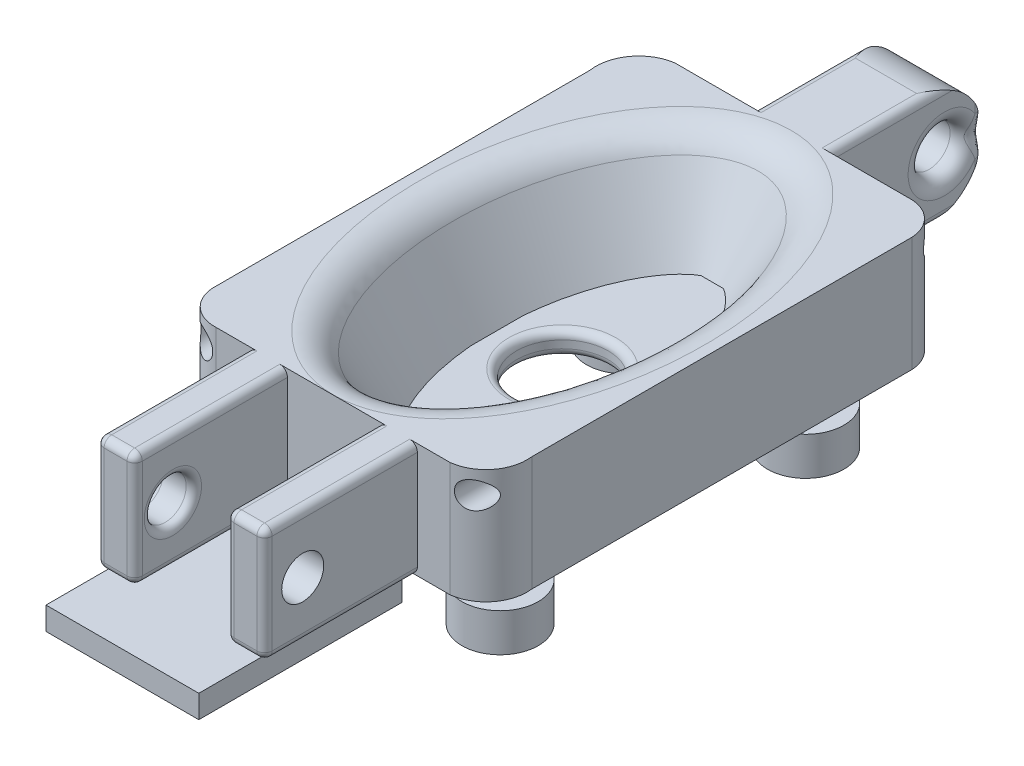
SolidWorks part; units mm, degrees
ref_plane "Front Plane" through (0, 0, 0) normal (0, 0, 1) x (1, 0, 0)
ref_plane "Top Plane" through (0, 0, 0) normal (0, 1, 0) x (1, 0, 0)
ref_plane "Right Plane" through (0, 0, 0) normal (1, 0, 0) x (0, 0, -1)
sketch "Sketch1" plane through (0, 0, 0) normal (0, 1, 0) x (1, 0, 0)
  line L1 (-15.3125, -30) -> (15.3125, -30)
  line L2 (-20, -25.7813) -> (-20, 23.5937)
  line L3 (-15.3125, 30) -> (15.3125, 30)
  line L4 (20, -24.0015) -> (20, 25.7812)
  line L5 (-20, -30) -> (20, 30) construction
  line L6 (-20, 30) -> (20, -30) construction
  arc A0 (-15.3125, 30) -> (-20, 23.5937) centre (-14.4531, 24.4531) ccw
  arc A1 (15.3125, 30) -> (20, 25.7812) centre (15.5469, 25.5469) cw
  arc A2 (15.3125, -30) -> (20, -24.0015) centre (14.657, -24.657) ccw
  arc A3 (-15.3125, -30) -> (-20, -25.7813) centre (-15.5469, -25.5469) cw
  point P0 (0, 0)
  dimension "D1" = 40
  dimension "D2" = 60
extrude "Boss-Extrude1" add sketch "Sketch1" along normal blind 15
sketch "Sketch2" plane through (0, 0, 30) normal (0, 0, 1) x (1, 0, 0)
  line L0 (-20, 15) -> (-20, 0) construction
  line L1 (20.0401, 0) -> (20.0401, 15) construction
  line L2 (15.3125, 0) -> (20.0401, 0) construction
  line L3 (-20, 0) -> (-15.3125, 0) construction
  circle A0 centre (-17.5, 12) radius 1.75
  circle A1 centre (17.5401, 12) radius 1.75
  dimension "D1" = 2.5
  dimension "D5" = 3.5
  dimension "D6" = 3.5
  dimension "D2" = 2.5
  dimension "D3" = 12
  dimension "D4" = 12
sketch "Sketch4" plane through (0, 15, 0) normal (0, 1, 0) x (1, 0, 0)
  ellipse E0 centre (0, 0) end of major axis (0, 27.1105) minor radius 15.7856
extrude "Cut-Extrude6" cut sketch "Sketch4" against normal blind 15 draft 30.5
fillet "Fillet4" radius 5 1 edges at (-2.7969, 15, -26.6816)
extrude "Cut-Extrude7" cut sketch "Sketch2" against normal blind 150
sketch "Sketch5" plane through (0, 0, 0) normal (0, -1, 0) x (1, 0, 0)
  line L1 (7.7139, -19.6019) -> (-8.5645, -19.6019)
  line L2 (7.7139, -19.6019) -> (7.7139, 20.1727)
  line L3 (7.7139, 20.1727) -> (-8.5645, 20.1727)
  line L4 (-8.5645, -19.6019) -> (-8.5645, 20.1727)
extrude "Boss-Extrude2" add sketch "Sketch5" against normal blind 3
sketch "Sketch6" plane through (0, 3, 0) normal (0, 1, 0) x (1, 0, 0)
  circle A0 centre (0, 0) radius 6
extrude "Cut-Extrude8" cut sketch "Sketch6" against normal blind 3
sketch "Sketch8" plane through (0, 0, -30) normal (0, 0, -1) x (-1, 0, 0)
  line L7 (-5, 15) -> (5, 15)
  line L8 (-5, 15) -> (-5, 0)
  line L9 (-5, 0) -> (5, 0)
  line L10 (5, 15) -> (5, 0)
  point P9 (0, 7.5)
extrude "Boss-Extrude3" add sketch "Sketch8" along normal blind 20
sketch "Sketch10" plane through (-5, 0, 0) normal (-1, 0, 0) x (0, 0, 1)
  line L0 (-50, 0) -> (-50, 15) construction
  line L1 (-50, 15) -> (-30, 15) construction
  circle A0 centre (-45, 7.32) radius 2.75
  dimension "D1" = 5
  dimension "D3" = 5.5
  dimension "D2" = 7.68
extrude "Cut-Extrude9" cut sketch "Sketch10" against normal blind 20
fillet "Fillet8" radius 2 1 edges at (5, 4.57, -45)
fillet "Fillet9" radius 1 1 edges at (-5, 4.57, -45)
fillet "Fillet11" radius 1 1 edges at (0, 15, -50)
fillet "Fillet12" radius 1 3 edges at (-5, 15, -39.5) (-5, 14.7071, -49.7071) (-5, 7, -50)
fillet "Fillet13" radius 1 3 edges at (5, 7, -50) (5, 15, -39.5) (5, 14.7071, -49.7071)
fillet "Fillet14" radius 1 5 edges at (-5, 0, -39.5) (-4.7071, 0, -49.7071) (5, 0, -39.5) (0, 0, -50) (4.7071, 0, -49.7071)
sketch "Sketch11" plane through (0, 0, 30) normal (0, 0, 1) x (1, 0, 0)
  line L3 (-10.98, 0) -> (-5.98, 0)
  line L10 (6.02, 0) -> (11.02, 0)
  line L15 (-5.98, 15) -> (-5.98, 0)
  line L20 (6.02, 15) -> (6.02, 0)
  line L25 (6.02, 0) -> (11.02, 0)
  line L26 (6.02, 0) -> (6.02, 15)
  line L27 (6.02, 15) -> (11.02, 15)
  line L28 (11.02, 0) -> (11.02, 15)
  line L30 (-5.98, 15) -> (-10.98, 15)
  line L31 (-5.98, 15) -> (-5.98, 0)
  line L32 (-5.98, 0) -> (-10.98, 0)
  line L33 (-10.98, 15) -> (-10.98, 0)
  point P7 (0.02, 7.5)
  line M22 (-15.3125, 0) -> (15.3125, 0)
  line M24 (15.3125, 15) -> (-15.3125, 15)
  dimension "D7" = 5
extrude "Boss-Extrude4" add sketch "Sketch11" along normal blind 20 contours L33 L15 M24 M22 | L28 L20 M22 M24
sketch "Sketch12" plane through (-10.98, 0, 0) normal (-1, 0, 0) x (0, 0, 1)
  line L0 (50, 0) -> (50, 15) construction
  line L1 (50, 15) -> (30, 15) construction
  circle A0 centre (45, 7.32) radius 2.75
  dimension "D1" = 5
  dimension "D3" = 5.5
  dimension "D2" = 7.68
extrude "Cut-Extrude10" cut sketch "Sketch12" against normal blind 250
fillet "Fillet17" radius 1 1 edges at (-10.98, 4.57, 45)
fillet "Fillet18" radius 1 1 edges at (-5.98, 7.32, 42.25)
fillet "Fillet19" radius 1 1 edges at (-5.98, 0, 40)
fillet "Fillet20" radius 1 3 edges at (-5.98, 8, 50) (-8.98, 0, 50) (-6.2729, 0.2929, 50)
fillet "Fillet21" radius 1 3 edges at (-10.98, 8, 50) (-10.98, 0, 39.5) (-10.98, 0.2929, 49.7071)
fillet "Fillet22" radius 1 5 edges at (-5.98, 15, 39.5) (-8.48, 15, 50) (-6.2729, 15, 49.7071) (-10.98, 15, 39.5) (-10.6871, 15, 49.7071)
fillet "Fillet23" radius 1 1 edges at (6.02, 0, 40)
fillet "Fillet25" radius 1 3 edges at (6.02, 8, 50) (9.02, 0, 50) (6.3129, 0.2929, 50)
fillet "Fillet26" radius 1 3 edges at (11.02, 0, 39.5) (11.02, 8, 50) (11.02, 0.2929, 49.7071)
fillet "Fillet27" radius 1 5 edges at (6.02, 15, 39.5) (6.3129, 15, 49.7071) (11.02, 15, 39.5) (8.52, 15, 50) (10.7271, 15, 49.7071)
fillet "Fillet28" radius 1 1 edges at (6.02, 7.32, 42.25)
fillet "Fillet29" radius 1 1 edges at (0, 0, 6)
fillet "Fillet30" radius 1 1 edges at (0, 3, 6)
sketch "Sketch13" plane through (0, 0, 0) normal (0, -1, 0) x (1, 0, 0)
  line L0 (-20, -23.5937) -> (-20, 25.7813) construction
  line L1 (20, 24.0015) -> (20, -25.7812) construction
  circle A0 centre (-11.8492, 20) radius 2.5
  circle A1 centre (11.85, 20) radius 2.5
  circle A2 centre (-11.8492, -20) radius 2.5
  circle A3 centre (11.85, -20) radius 2.5
  dimension "D1" = 5
  dimension "D4" = 5
  dimension "D7" = 5
  dimension "D8" = 5
  dimension "D2" = 8.1508
  dimension "D3" = 20
  dimension "D5" = 8.15
  dimension "D6" = 20
  dimension "D9" = 8.1508
  dimension "D10" = 8.15
  dimension "D11" = 20
  dimension "D12" = 20
extrude "Boss-Extrude5" add sketch "Sketch13" along normal blind 5 draft 7
sketch "Sketch14" plane through (0, -5, 0) normal (0, -1, 0) x (1, 0, 0)
  circle A0 centre (-11.8492, 20) radius 5
  circle A1 centre (11.85, 20) radius 5
  circle A2 centre (11.85, -20) radius 5
  circle A3 centre (-11.8492, -20) radius 5
  dimension "D1" = 10
  dimension "D2" = 10
  dimension "D3" = 10
  dimension "D4" = 10
extrude "Boss-Extrude6" add sketch "Sketch14" along normal blind 5
sketch "Sketch19" plane through (0, 0, 0) normal (0, -1, 0) x (1, 0, 0)
  line L0 (10.02, 30) -> (10.02, 49) construction
  line L2 (-9.98, 49) -> (-9.98, 31)
  line L3 (-9.98, 31) -> (10.02, 31)
  line L4 (10.02, 49) -> (10.02, 31)
  line L8 (10.02, 49) -> (10.02, 57.6029)
  line L9 (10.02, 57.6029) -> (-9.98, 57.6029)
  line L10 (-9.98, 49) -> (-9.98, 57.6029)
  dimension "D1" = 18
extrude "Boss-Extrude14" add sketch "Sketch19" along normal blind 3
sketch "Sketch24" plane through (-5, 0, 0) normal (-1, 0, 0) x (0, 0, 1)
  line L0 (-49, 15) -> (-30, 15) construction
  line L1 (-30, 0) -> (-49, 0) construction
  line L3 (-42.0784, 15) -> (-50.6216, 15)
  line L5 (-42.0784, -0.0041) -> (-50.6216, -0.0041)
  line L6 (-50.6216, 15) -> (-50.6216, -0.0041)
  arc A1 (-50.0388, 7.32) -> (-42.0784, 15) centre (-42.2186, 7.1798) cw
  arc A2 (-42.2186, 0) -> (-50.0388, 7.32) centre (-42.4687, 7.5701) cw
  line M3 (-49, 14) -> (-49, 1)
  line M4 (-49, 1) -> (-30, 1)
  line M6 (-30, 14) -> (-49, 14)
  dimension "D1" = 8.5432
extrude "Cut-Extrude11" cut sketch "Sketch24" against normal blind 25 contours A1 M3 M6 | A2 A1 L3 L6 L5 M3 M6 M4 | A2 M4 M3
